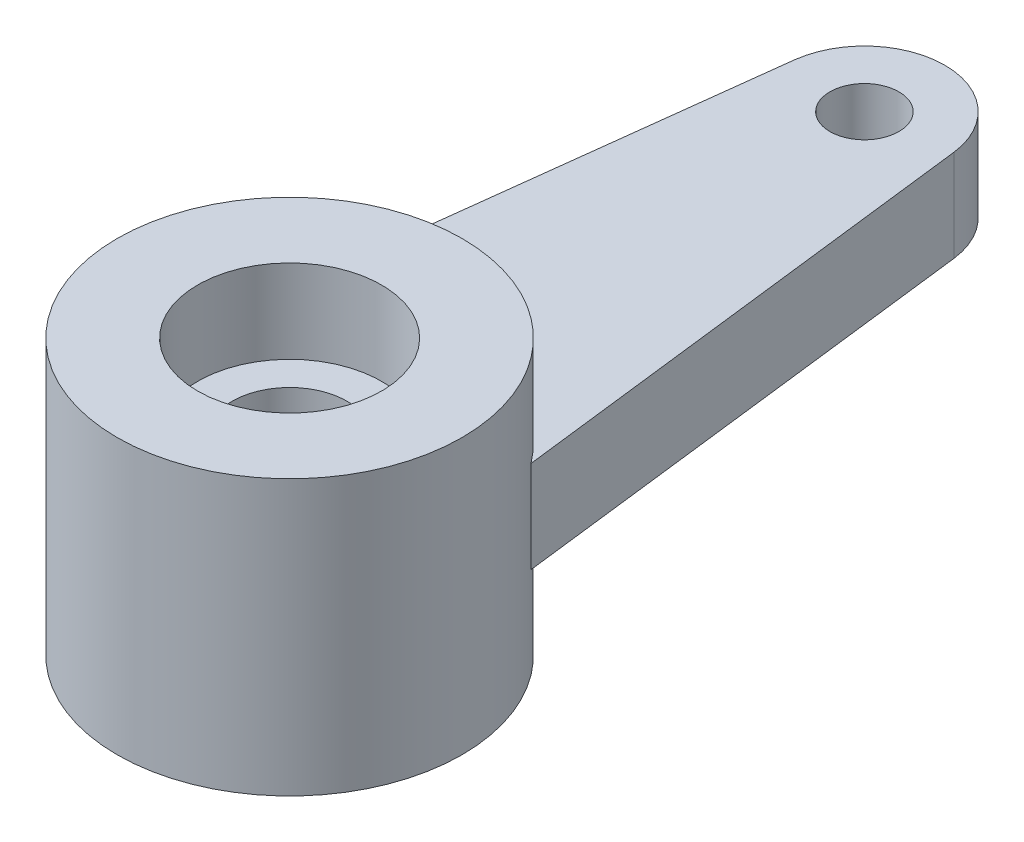
SolidWorks part; units mm, degrees
ref_plane "Front Plane" through (0, 0, 0) normal (0, 0, 1) x (1, 0, 0)
ref_plane "Top Plane" through (0, 0, 0) normal (0, 1, 0) x (1, 0, 0)
ref_plane "Right Plane" through (0, 0, 0) normal (1, 0, 0) x (0, 0, -1)
sketch "Sketch1" plane through (0, 0, 0) normal (0, 1, 0) x (1, 0, 0)
  line L0 (0, 0) -> (0, 22841.5203) construction
  line L1 (0, 0) -> (22841.5203, 0) construction
  circle A0 centre (0, 0) radius 7.5
  dimension "D1" = 15
extrude "Boss-Extrude1" add sketch "Sketch1" along normal mid plane 11.95
sketch "Sketch2" plane through (0, 5.975, 0) normal (0, 1, 0) x (1, 0, 0)
  circle A0 centre (0, 0) radius 2.5
  dimension "D1" = 5
extrude "Rod-Cutout" cut sketch "Sketch2" against normal through all and the other way through all
sketch "Sketch3" plane through (0, 5.975, 0) normal (0, 1, 0) x (1, 0, 0)
  circle A0 centre (0, 0) radius 4
  dimension "D1" = 8
extrude "Bearing-Cutout" cut sketch "Sketch3" against normal blind 3.63
mirror "Mirror1" about plane through (0, 0, 0) normal (0, 1, 0) of "Bearing-Cutout"
sketch "Sketch4" plane through (0, 0, 0) normal (0, 1, 0) x (1, 0, 0)
  line L0 (0, 0) -> (0, -50000) construction
  line L1 (0, 0) -> (-50000, 0) construction
  line L2 (-6, 0) -> (6, 0)
  line L3 (6, 0) -> (6, 4.5)
  line L4 (6, 4.5) -> (3.4748, 25.4194)
  line L5 (-6, 0) -> (-6, 4.5)
  line L6 (-6, 4.5) -> (-3.4748, 25.4194)
  circle A0 centre (0, 0) radius 7.5 construction
  arc A1 (3.4748, 25.4194) -> (-3.4748, 25.4194) centre (0, 25) ccw
  point P26 (0, 0)
  dimension "D1" = 7
  dimension "D2" = 12
  dimension "D3" = 25
extrude "SteeringLink-Mount" add sketch "Sketch4" along normal mid plane 4
sketch "Sketch5" plane through (0, 5.975, 0) normal (0, 1, 0) x (1, 0, 0)
  circle A0 centre (0, 0) radius 2.5
  circle A1 centre (0, 0) radius 2.5 construction
extrude "Cut-Extrude3" cut sketch "Sketch5" against normal through all
sketch "Sketch6" plane through (0, 2, 0) normal (0, 1, 0) x (1, 0, 0)
  line L0 (0, 0) -> (0, 50000) construction
  circle A0 centre (0, 25) radius 3.5 construction
  arc A1 (3.4748, 25.4194) -> (-3.4748, 25.4194) centre (0, 25) ccw construction
  circle A2 centre (0, 25) radius 1.5
  dimension "D1" = 3
extrude "LinkageMount-Hole" cut sketch "Sketch6" against normal blind 10
